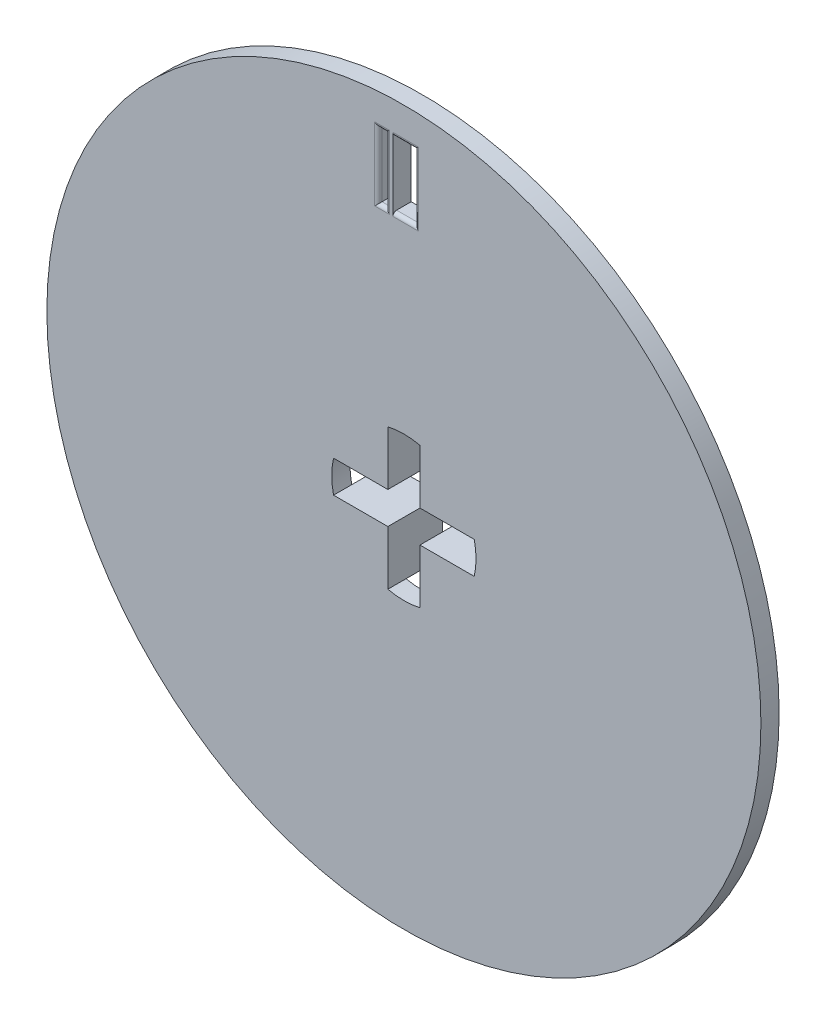
SolidWorks part; units mm, degrees
ref_plane "Front Plane" through (0, 0, 0) normal (0, 0, 1) x (1, 0, 0)
ref_plane "Top Plane" through (0, 0, 0) normal (0, 1, 0) x (1, 0, 0)
ref_plane "Right Plane" through (0, 0, 0) normal (1, 0, 0) x (0, 0, -1)
sketch "Sketch1" plane through (0, 0, 0) normal (0, 0, 1) x (1, 0, 0)
  line L0 (0, 9.9) -> (0, 40)
  line L1 (-1.5, 44.5) -> (-2.5, 44.5)
  line L2 (-1.5, 44.5) -> (1.5, 44.5)
  line L3 (-1.5, 44.5) -> (-1.5, 35.5)
  line L4 (-1.5, 35.5) -> (1.5, 35.5)
  line L5 (1.5, 44.5) -> (1.5, 35.5)
  line L6 (-1.5, 44.5) -> (1.5, 35.5) construction
  line L7 (-1.5, 35.5) -> (1.5, 44.5) construction
  line L8 (-2.5, 44.5) -> (-2.5, 35.5)
  line L9 (-2.5, 35.5) -> (-3.5, 35.5)
  line L10 (-3.5, 35.5) -> (-3.5, 44.5)
  line L11 (-3.5, 44.5) -> (-2.5, 44.5)
  line L12 (0, -9.9) -> (0, -40)
  line L14 (-1.5, -35.5) -> (1.5, -35.5)
  line L15 (-1.5, -35.5) -> (-1.5, -44.5)
  line L16 (-1.5, -44.5) -> (1.5, -44.5)
  line L17 (1.5, -35.5) -> (1.5, -44.5)
  line L18 (-1.5, -35.5) -> (1.5, -44.5) construction
  line L19 (-1.5, -44.5) -> (1.5, -35.5) construction
  line L24 (-3.5, -35.5) -> (-2.5, -35.5)
  line L29 (-1.8473, 9.7261) -> (1.8473, -9.7261) construction
  line L30 (-1.8473, -9.7261) -> (1.8473, 9.7261) construction
  line L35 (-9.7507, 1.7127) -> (9.7507, -1.7127) construction
  line L36 (-9.7507, -1.7127) -> (9.7507, 1.7127) construction
  line L37 (-3.5, -44.5) -> (-3.5, -35.5)
  line L38 (-2.5, -44.5) -> (-3.5, -44.5)
  line L39 (-2.5, -35.5) -> (-2.5, -44.5)
  line L43 (9.6525, -2.2) -> (-9.6525, -2.2)
  line L44 (9.6525, 2.2) -> (-9.6525, 2.2)
  line L45 (2.2, -9.6525) -> (2.2, 9.6525)
  line L46 (-2.2, -9.6525) -> (-2.2, 9.6525)
  circle A0 centre (0, 0) radius 49
  circle A1 centre (0, 0) radius 9.9
  dimension "D1" = 98
  dimension "D2" = 19.8
  dimension "D3" = 9
  dimension "D4" = 3
  dimension "D5" = 9
  dimension "D6" = 3
extrude "Boss-Extrude1" add sketch "Sketch1" along normal blind 2.5 contours A0 A1 L4 L3 L8 L9 L10 L11 L2 L5 L14 L17 L16 L15 | L17 L14 L15 L16 | L39 L24 L37 L38 region at (0.75, -35.5949, 0) region at (-3, -40, 0) region at (-47.6141, 0, 0)
extrude "Boss-Extrude2" add sketch "Sketch1<3>" against normal blind 5 contours A1 | A1 | A1 | A1 region at (5.1546, 5.1546, 0) region at (-5.1546, 5.1546, 0) region at (5.1546, -5.1546, 0) region at (-5.1546, -5.1546, 0)
sketch "Sketch1<3>" plane through (0, 0, 0) normal (0, 0, 1) x (1, 0, 0) same geometry as "Sketch1"
fillet "Fillet1" radius 0.5 7 edges at (-3, 44.5, 2.5) (-3, 35.5, 2.5) (-2.5, 40, 2.5) (-3.5, 40, 2.5) (0, 44.5, 2.5) (1.5, 40, 2.5) (0, 35.5, 2.5)
sketch "Sketch3" plane through (0, 0, 0) normal (0, 0, 1) x (1, 0, 0)
  line L2 (-2.2, 2.2) -> (-2.2, 9.6525)
  line L3 (-2.2, 2.2) -> (-2.2, 9.6525)
  line L4 (9.6525, -2.2) -> (2.2, -2.2)
  line L6 (-2.2, -2.2) -> (-9.6525, -2.2)
  line L7 (-9.6525, 2.2) -> (-2.2, 2.2)
  line L9 (-9.6525, 2.2) -> (-2.2, 2.2)
  line L11 (-2.2, -2.2) -> (-9.6525, -2.2)
  line L12 (2.2, -2.2) -> (2.2, -9.6525)
  line L14 (2.2, -2.2) -> (2.2, -9.6525)
  line L16 (9.6525, -2.2) -> (2.2, -2.2)
  line L17 (-2.2, -9.6525) -> (-2.2, -2.2)
  line L18 (2.2, 2.2) -> (9.6525, 2.2)
  line L19 (2.2, 9.6525) -> (2.2, 2.2)
  line L20 (2.2, 2.2) -> (9.6525, 2.2)
  line L21 (2.2, 9.6525) -> (2.2, 2.2)
  line L22 (-2.2, -9.6525) -> (-2.2, -2.2)
  arc A3 (-2.2, 9.6525) -> (-9.6525, 2.2) centre (0, 0) ccw
  arc A4 (-2.2, 9.6525) -> (-9.6525, 2.2) centre (0, 0) ccw
  arc A6 (2.2, -9.6525) -> (9.6525, -2.2) centre (0, 0) ccw
  arc A7 (2.2, -9.6525) -> (9.6525, -2.2) centre (0, 0) ccw
  arc A9 (9.6525, 2.2) -> (2.2, 9.6525) centre (0, 0) ccw
  arc A10 (9.6525, 2.2) -> (2.2, 9.6525) centre (0, 0) ccw
  arc A12 (-9.6525, -2.2) -> (-2.2, -9.6525) centre (0, 0) ccw
  arc A13 (-9.6525, -2.2) -> (-2.2, -9.6525) centre (0, 0) ccw
  dimension "D1" = 0
  dimension "D2" = 0
  dimension "D3" = 0
  dimension "D4" = 0
extrude "Boss-Extrude4" add sketch "Sketch3" along normal blind 2.5
